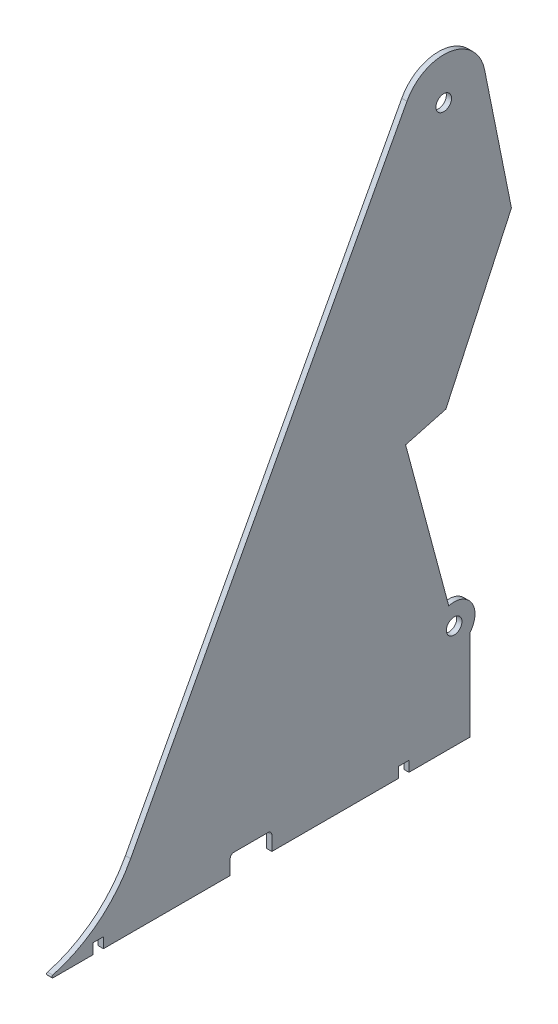
SolidWorks part; units mm, degrees
ref_plane "Front Plane" through (0, 0, 0) normal (0, 0, 1) x (1, 0, 0)
ref_plane "Top Plane" through (0, 0, 0) normal (0, 1, 0) x (1, 0, 0)
ref_plane "Right Plane" through (0, 0, 0) normal (1, 0, 0) x (0, 0, -1)
sketch "Sketch1" plane through (0, 0, 0) normal (1, 0, 0) x (0, 0, -1)
  line L0 (0, 0) -> (0, 55.0997)
  line L6 (-39.108, 173.9053) -> (-14.5735, 180.4793)
  line L7 (-14.5735, 180.4793) -> (25.4, 266.7)
  line L8 (25.4, 266.7) -> (9.0239, 347.9203)
  line L9 (-38.2834, 354.8592) -> (-206.7022, 39.2864)
  line L10 (-254, 0) -> (0, 0)
  line L12 (-254.2054, 1.5605) -> (-207.9989, 13.9415) construction
  line L13 (-39.108, 173.9053) -> (-12.812, 75.7673)
  line L14 (-12.812, 75.7673) -> (13.738, 82.8813) construction
  arc A0 (9.0239, 347.9203) -> (-38.2834, 354.8592) centre (-15.875, 342.9) ccw
  arc A1 (-254, 0) -> (-254.2054, 1.5605) centre (-254, 0.7937) cw
  arc A2 (-254.2054, 1.5605) -> (-206.7022, 39.2864) centre (-273.9274, 75.164) ccw
  arc A3 (0, 55.0997) -> (-12.812, 75.7673) centre (-9.525, 63.5) ccw
  dimension "D2" = 25.4
  dimension "D6" = 0.7937
  dimension "D7" = 76.2
  dimension "D12" = 12.7
  dimension "D1" = 15.875
  dimension "D3" = 342.9
  dimension "D4" = 25.4
  dimension "D5" = 101.6
  dimension "D8" = 254
  dimension "D9" = 15
  dimension "D10" = 9.525
  dimension "D11" = 63.5
  dimension "D13" = 76.2
  dimension "D14" = 25.4
  dimension "D15" = 15
extrude "Boss-Extrude1" add sketch "Sketch1" along normal blind 3.175
sketch "Sketch2" plane through (3.175, 0, 0) normal (1, 0, 0) x (0, 0, -1)
  line L16 (-146.05, 8.7909) -> (-146.05, -0.3034) construction
  line L17 (-123.0376, 11.1785) -> (-143.6624, 11.1785) construction
  line L18 (-120.65, -0.3034) -> (-120.65, 8.7909) construction
  line L19 (-146.05, 8.7909) -> (-146.05, 0)
  line L20 (-123.0376, 11.1785) -> (-143.6624, 11.1785)
  line L21 (-120.65, 0) -> (-120.65, 8.7909)
  line L23 (-37.0504, 0) -> (-37.0504, 6.35) construction
  line L24 (-43.4004, 0) -> (-37.0504, 0) construction
  line L25 (-146.05, 0) -> (-120.65, 0)
  line L26 (-254, 0) -> (0, 0) construction
  line L27 (-43.4004, 6.35) -> (-43.4004, 0) construction
  line L28 (-37.0504, 6.35) -> (-43.4004, 6.35) construction
  line L29 (-37.0504, 0) -> (-37.0504, 6.35)
  line L30 (-43.4004, 0) -> (-37.0504, 0)
  line L31 (-43.4004, 6.35) -> (-43.4004, 0)
  line L32 (-37.0504, 6.35) -> (-43.4004, 6.35)
  line L33 (-223.2996, 0) -> (-223.2996, 6.35) construction
  line L34 (-229.6496, 0) -> (-223.2996, 0) construction
  line L35 (-229.6496, 6.35) -> (-229.6496, 0) construction
  line L36 (-223.2996, 6.35) -> (-229.6496, 6.35) construction
  line L37 (-223.2996, 0) -> (-223.2996, 6.35)
  line L38 (-229.6496, 0) -> (-223.2996, 0)
  line L39 (-229.6496, 6.35) -> (-229.6496, 0)
  line L40 (-223.2996, 6.35) -> (-229.6496, 6.35)
  arc A0 (-143.6624, 11.1785) -> (-146.05, 8.7909) centre (-143.6624, 8.7909) ccw construction
  arc A1 (-120.65, 8.7909) -> (-123.0376, 11.1785) centre (-123.0376, 8.7909) ccw construction
  arc A2 (-143.6624, 11.1785) -> (-146.05, 8.7909) centre (-143.6624, 8.7909) ccw
  arc A3 (-120.65, 8.7909) -> (-123.0376, 11.1785) centre (-123.0376, 8.7909) ccw
extrude "Cut-Extrude1" cut sketch "Sketch2" against normal through all
sketch "Sketch3" plane through (3.175, 0, 0) normal (1, 0, 0) x (0, 0, -1)
  point P0 (-15.875, 342.9)
  point P4 (-9.525, 63.5)
hole_wizard "3/8 Clearance Hole1" positions "Sketch3" profile "Sketch4" hole size "3/8" standard "ANSI Inch" end condition up to next
sketch "Sketch4" plane through (3.175, 342.9, 15.875) normal (0, 1, 0) x (0, 0, -1)
  line L0 (0, 0) -> (0, 3.175)
  line L1 (0, 3.175) -> (4.7625, 3.175)
  line L2 (4.7625, 3.175) -> (4.7625, 0)
  line L5 (4.7625, 0) -> (0, 0)
  line L11 (0, -6.35) -> (0, 107.95) construction
  dimension "Thru Hole Dia." = 9.525
  dimension "Thru Hole Depth" = 3.175
sketch "Sketch5" plane through (3.175, 0, 0) normal (1, 0, 0) x (0, 0, -1)
  line L0 (-9.525, 63.5) -> (26.6637, 27.8487)
  line L1 (26.6637, 27.8487) -> (26.7576, 15.3058)
  line L2 (22.1401, 32.3051) -> (-24.5595, 22.9623)
  line L3 (-15.875, 19.05) -> (-24.5595, 22.9623)
  line L4 (0, 0) -> (0, 55.0997) construction
  line L5 (-15.875, 19.05) -> (-33.6895, 12.3011)
  line L6 (-33.6895, 12.3011) -> (-54.7505, 169.5016)
  line L7 (50.8, 0) -> (50.8, 73.5762) construction
  dimension "D1" = 44.45
  dimension "D2" = 50.8
  dimension "D3" = 45
  dimension "D4" = 60.325
  dimension "D5" = 19.05
  dimension "D6" = 15.875
  dimension "D7" = 9.525
  dimension "D8" = 47.625
  dimension "D9" = 19.05
  dimension "D10" = 45
  dimension "D11" = 50.8
sketch "Sketch6" [suppressed] plane through (3.175, 0, 0) normal (1, 0, 0) x (0, 0, -1)
  line L0 (-135.2155, 112.2463) -> (-149.7697, 112.2463) construction
  line L1 (-149.7697, 112.2463) -> (-163.7749, 119.7208) construction
  line L3 (-38.2834, 354.8592) -> (-206.7022, 39.2864) construction
  circle A0 centre (-135.2155, 112.2463) radius 3.81
  circle A1 centre (-114.8836, 103.0188) radius 2.032
  circle A2 centre (-149.7697, 112.2463) radius 2.032
  dimension "D1" = 7.62
  dimension "D3" = 4.064
  dimension "D4" = 4.064
  dimension "D2" = 14.5542
  dimension "D5" = 15.875
  dimension "D6" = 266.7
extrude "Cut-Extrude2" [suppressed] cut sketch "Sketch6" against normal through all
